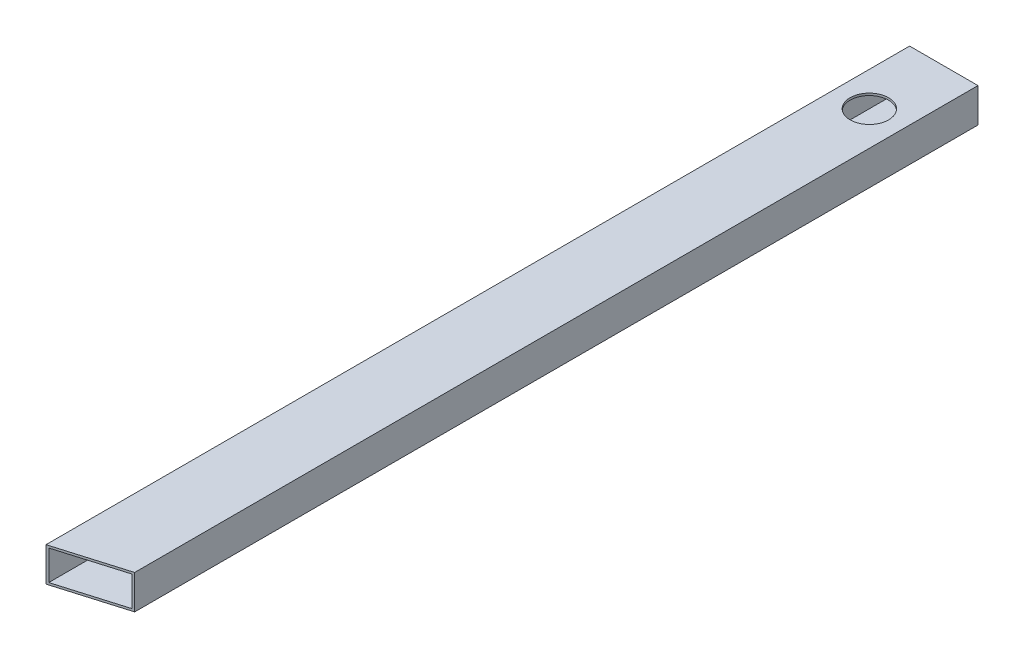
SolidWorks part; units mm, degrees
ref_plane "Front Plane" through (0, 0, 0) normal (0, 0, 1) x (1, 0, 0)
ref_plane "Top Plane" through (0, 0, 0) normal (0, 1, 0) x (1, 0, 0)
ref_plane "Right Plane" through (0, 0, 0) normal (1, 0, 0) x (0, 0, -1)
sketch "Sketch1" plane through (0, 0, 0) normal (0, 0, 1) x (1, 0, 0)
  line L0 (-23.8125, 11.1125) -> (23.8125, 11.1125)
  line L2 (-25.4, 12.7) -> (25.4, 12.7)
  line L3 (-25.4, 12.7) -> (-25.4, -12.7)
  line L4 (-25.4, -12.7) -> (25.4, -12.7)
  line L5 (25.4, 12.7) -> (25.4, -12.7)
  line L10 (23.8125, 11.1125) -> (23.8125, -11.1125)
  line L11 (-23.8125, -11.1125) -> (23.8125, -11.1125)
  line L12 (-23.8125, 11.1125) -> (-23.8125, -11.1125)
  point P12 (0, 12.7)
  point P14 (25.4, 0)
  dimension "Wall Thickness" = 1.5875
  dimension "Outside Width" = 50.8
  dimension "Outside Height" = 25.4
  dimension "Inside Height" = 22.225
  dimension "Inside Width" = 47.625
sketch "Sketch2" plane through (0, 0, 0) normal (1, 0, 0) x (0, 0, -1)
  line L0 (320.675, 0) -> (-320.675, 0)
  point P4 (0, 0)
  point P7 (-320.675, 0)
  point P10 (320.675, 0)
  dimension "Length" = 641.35
sketch "Sketch3" plane through (0, 0, 0) normal (0, 0, 1) x (1, 0, 0)
  line L21 (25.4, 12.7) -> (-25.4, 12.7)
  line L22 (25.4, -12.7) -> (25.4, 12.7)
  line L23 (-25.4, -12.7) -> (25.4, -12.7)
  line L24 (-25.4, 12.7) -> (-25.4, -12.7)
  line L25 (25.4, 12.7) -> (-25.4, 12.7)
  line L26 (25.4, -12.7) -> (25.4, 12.7)
  line L27 (-25.4, -12.7) -> (25.4, -12.7)
  line L28 (-25.4, 12.7) -> (-25.4, -12.7)
  line L29 (23.8125, 11.1125) -> (-23.8125, 11.1125)
  line L30 (23.8125, -11.1125) -> (23.8125, 11.1125)
  line L31 (-23.8125, -11.1125) -> (23.8125, -11.1125)
  line L32 (-23.8125, 11.1125) -> (-23.8125, -11.1125)
  line L33 (23.8125, 11.1125) -> (-23.8125, 11.1125)
  line L34 (23.8125, -11.1125) -> (23.8125, 11.1125)
  line L35 (-23.8125, -11.1125) -> (23.8125, -11.1125)
  line L36 (-23.8125, 11.1125) -> (-23.8125, -11.1125)
  dimension "D1" = 0
  dimension "D2" = 0
extrude "Boss-Extrude1" add sketch "Sketch3" along normal up to vertex (320.675 mm away) and the other way up to vertex (320.675 mm away) up to point (0, 0, 320.675) other way up to point (0, 0, -320.675)
sketch "Drawing Reference" plane through (0, 0, 0) normal (1, 0, 0) x (0, 0, -1)
  line L0 (-320.675, 0) -> (320.675, 0) construction
  line L1 (0, -12.7) -> (0, 12.7) construction
  line L2 (-320.675, -12.7) -> (320.675, -12.7) construction
  line L5 (-320.675, 12.7) -> (320.675, 12.7) construction
  point P7 (-284.099, 0)
  point P8 (284.099, 0)
  dimension "D1" = 36.576
sketch "Sketch4" plane through (0, 12.7, 0) normal (0, 1, 0) x (1, 0, 0)
  line L0 (-25.4, -320.675) -> (25.4, -305.6274)
  line L1 (25.4, -320.675) -> (25.4, 320.675) construction
  line L2 (25.4, -320.675) -> (-25.4, -320.675)
  dimension "D1" = 16.5
extrude "Cut-Extrude1" cut sketch "Sketch4" against normal through all and the other way through all flip side to cut
sketch "Sketch8" plane through (0, 12.7, 0) normal (0, 1, 0) x (1, 0, 0)
  line L0 (0, 320.675) -> (0, 265.3884) construction
  line L1 (25.4, 320.675) -> (-25.4, 320.675) construction
  circle A0 centre (0, 265.3884) radius 14.2875
extrude "Cut-Extrude2" cut sketch "Sketch8" against normal through all
equation "\"D1@Drawing Reference\"=\"Outside Width@Sketch1\" * 0.72"
